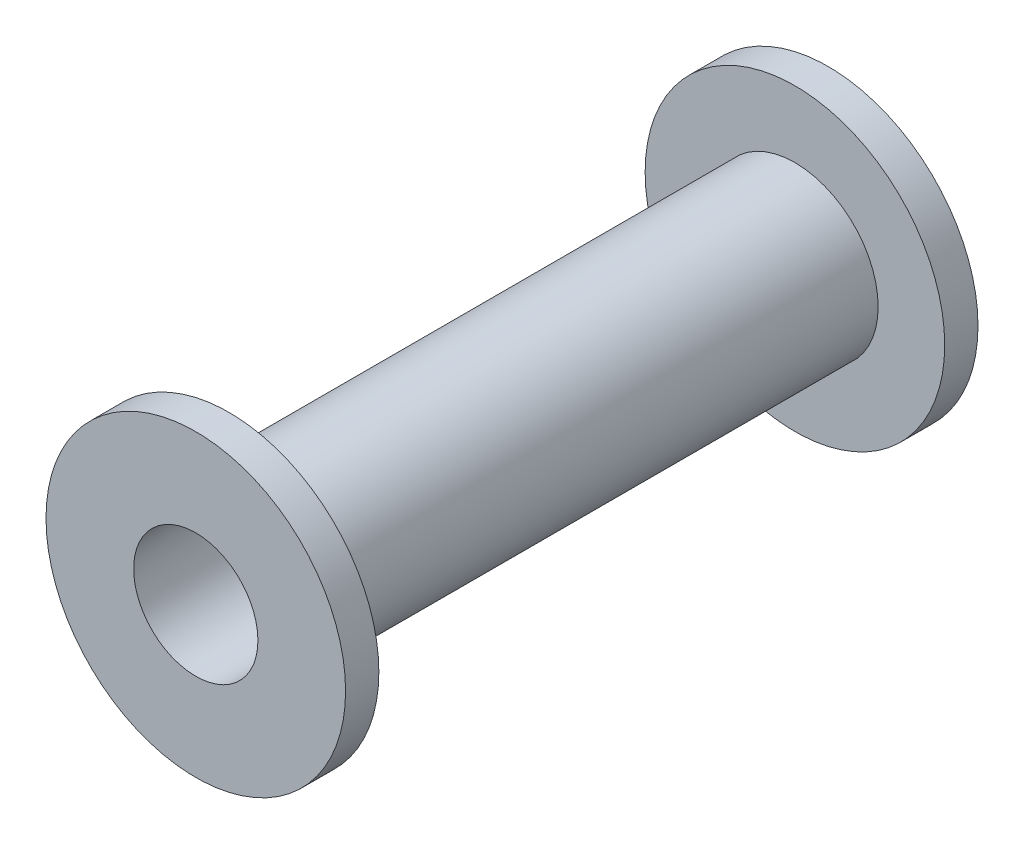
SolidWorks part; units mm, degrees
material "Filme de alta densidade PE"
ref_plane "Plano frontal" through (0, 0, 0) normal (0, 0, 1) x (1, 0, 0)
ref_plane "Plano superior" through (0, 0, 0) normal (0, 1, 0) x (1, 0, 0)
ref_plane "Plano direito" through (0, 0, 0) normal (1, 0, 0) x (0, 0, -1)
sketch "Esboço1" plane through (0, 0, 0) normal (0, 0, 1) x (1, 0, 0)
  circle A0 centre (0, 0) radius 5.6
  circle A1 centre (0, 0) radius 13.5
  dimension "D1" = 11.2
  dimension "D2" = 27
extrude "Ressalto-extrusão1" add sketch "Esboço1" along normal blind 3
sketch "Esboço2" plane through (0, 0, 3) normal (0, 0, 1) x (1, 0, 0)
  circle A0 centre (0, 0) radius 7.5
  circle A1 centre (0, 0) radius 5.6
  circle A2 centre (0, 0) radius 5.6 construction
  dimension "D1" = 15
extrude "Ressalto-extrusão2" add sketch "Esboço2" along normal blind 51
sketch "Esboço3" plane through (0, 0, 54) normal (0, 0, 1) x (1, 0, 0)
  circle A0 centre (0, 0) radius 13.5
  circle A1 centre (0, 0) radius 5.6
  circle A2 centre (0, 0) radius 5.6 construction
  dimension "D2" = 27
extrude "Ressalto-extrusão3" add sketch "Esboço3" along normal blind 3
sketch "Esboço6" plane through (0, 0, 0) normal (0, 0, -1) x (-1, 0, 0)
  line L0 (0, 0) -> (0, 9) construction
  dimension "D1" = 9
